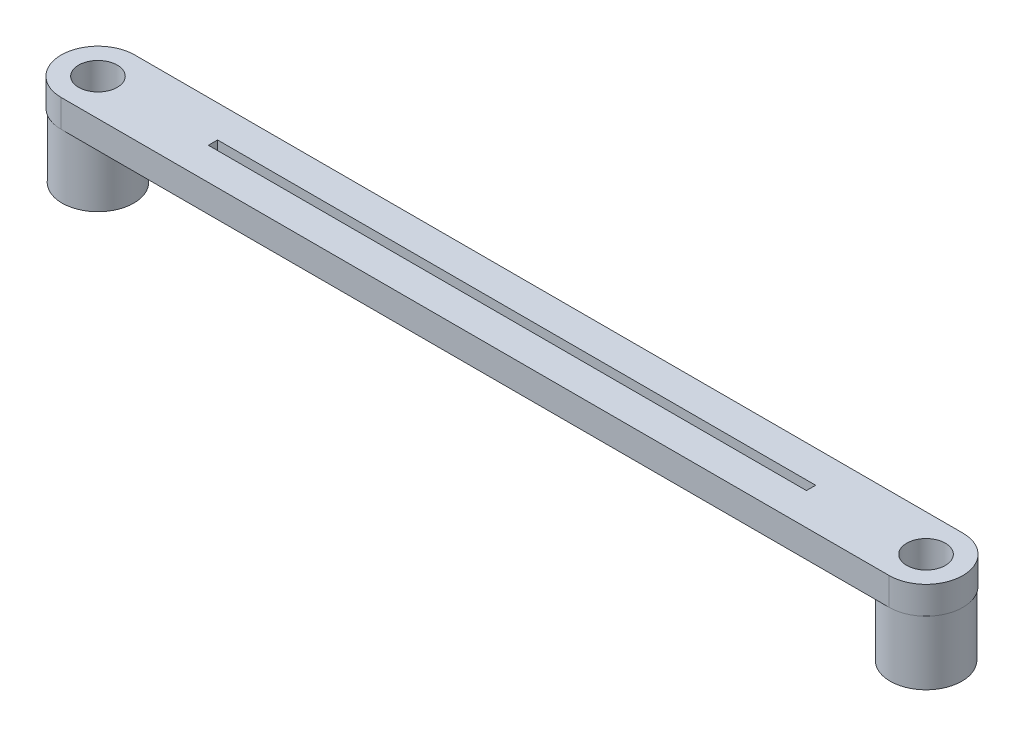
SolidWorks part; units mm, degrees
ref_plane "Front Plane" through (0, 0, 0) normal (0, 0, 1) x (1, 0, 0)
ref_plane "Top Plane" through (0, 0, 0) normal (0, 1, 0) x (1, 0, 0)
ref_plane "Right Plane" through (0, 0, 0) normal (1, 0, 0) x (0, 0, -1)
sketch "Sketch1" plane through (0, 0, 0) normal (0, 1, 0) x (1, 0, 0)
  line L0 (-45, 0) -> (45, 0) construction
  line L1 (-45, 4) -> (45, 4)
  line L2 (-45, -4) -> (45, -4)
  arc A0 (-45, 4) -> (-45, -4) centre (-45, 0) ccw
  arc A1 (45, -4) -> (45, 4) centre (45, 0) ccw
  circle A2 centre (-45, 0) radius 2.1
  circle A3 centre (45, 0) radius 2.1
  point P2 (0, 0)
  dimension "D3" = 4.2
  dimension "D1" = 90
  dimension "D2" = 8
extrude "Boss-Extrude1" add sketch "Sketch1" against normal blind 3
sketch "Sketch2" plane through (0, -3, 0) normal (0, -1, 0) x (1, 0, 0)
  circle A0 centre (45, 0) radius 2.1 construction
  circle A1 centre (-45, 0) radius 2.1 construction
  circle A2 centre (45, 0) radius 2.1
  circle A3 centre (-45, 0) radius 2.1
extrude "Extrude-Thin1" add sketch "Sketch2" along normal blind 7 thin thin type one direction wall 1.8
sketch "Sketch3" plane through (0, 0, 0) normal (0, 1, 0) x (1, 0, 0)
  line L1 (32.5, -0.5) -> (-32.5, -0.5)
  line L2 (32.5, -0.5) -> (32.5, 0.5)
  line L3 (32.5, 0.5) -> (-32.5, 0.5)
  line L4 (-32.5, -0.5) -> (-32.5, 0.5)
  line L5 (0, 0.5) -> (0, -0.5) construction
  line L6 (32.5, 0) -> (-32.5, 0) construction
  point P0 (0, 0)
  dimension "D1" = 1
  dimension "D2" = 65
extrude "Cut-Extrude1" cut sketch "Sketch3" against normal blind 1
